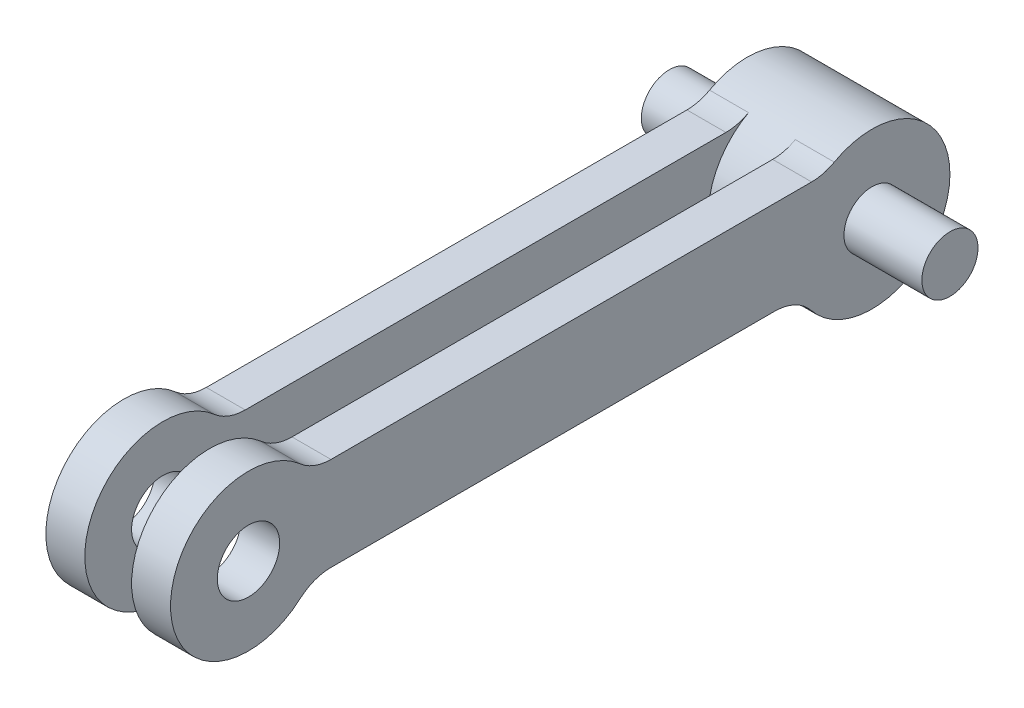
SolidWorks part; units mm, degrees
ref_plane "前视基准面" through (0, 0, 0) normal (0, 0, 1) x (1, 0, 0)
ref_plane "上视基准面" through (0, 0, 0) normal (0, 1, 0) x (1, 0, 0)
ref_plane "右视基准面" through (0, 0, 0) normal (1, 0, 0) x (0, 0, -1)
other "Configuration Table"
sketch "草图1" plane through (0, 0, 0) normal (1, 0, 0) x (0, 0, -1)
  line L1 (0, -3) -> (40, -3)
  line L2 (0, -3) -> (0, 3)
  line L3 (0, 3) -> (40, 3)
  line L4 (40, -3) -> (40, 3)
  circle A0 centre (0, 0) radius 5
  circle A1 centre (40, -1) radius 5
  circle A2 centre (0, 0) radius 2
  circle A3 centre (40, -1) radius 2
  dimension "D1" = 4
  dimension "D4" = 10
  dimension "D5" = 10
  dimension "D2" = 6
  dimension "D3" = 2
  dimension "D6" = 40
extrude "凸台-拉伸1" add sketch "草图1" along normal blind 2.5 contours A0 | L3 L4 L1 L2 | A1
extrude "切除-拉伸2" cut sketch "草图1<3>" against normal through all and the other way through all contours A2 | A3
sketch "草图1<3>" plane through (0, 0, 0) normal (1, 0, 0) x (0, 0, -1) same geometry as "草图1"
fillet "圆角1" radius 3 4 edges at (1.25, -3, -4) (1.25, -3, -35.4174) (1.25, 3, -37) (1.25, 3, -4)
extrude "凸台-拉伸2" add sketch "草图1<4>" against normal blind 1.5 contours A3 L1 A1 L3 L4 | A3 L4 L3 A1 L1 region at (0, 0.0971, -37.2585) region at (0, -3.1385, -37.7087)
sketch "草图1<4>" plane through (0, 0, 0) normal (1, 0, 0) x (0, 0, -1) same geometry as "草图1"
sketch "草图2" plane through (2.5, 0, 0) normal (1, 0, 0) x (0, 0, -1)
  circle A0 centre (40, -1) radius 2
  circle A1 centre (40, -1) radius 1.8
  circle A2 centre (40, -1) radius 2 construction
  dimension "D1" = 3.6
extrude "凸台-拉伸4" add sketch "草图2" along normal blind 5 contours A1 region at (2.5, -1, -40)
extrude "凸台-拉伸5" add sketch "草图1<5>" along normal up to surface and the other way up to surface contours A3 up to face at (2.5, 0, -2) other way up to face at (-1.5, -1, -42)
sketch "草图1<5>" plane through (0, 0, 0) normal (1, 0, 0) x (0, 0, -1) same geometry as "草图1"
ref_plane "基准面1" through (-1.5, 0, 0) normal (-1, 0, 0) x (0, 0, 1)
mirror "镜向3" about plane through (-1.5, 0, 0) normal (-1, 0, 0) of bodies 114 108
